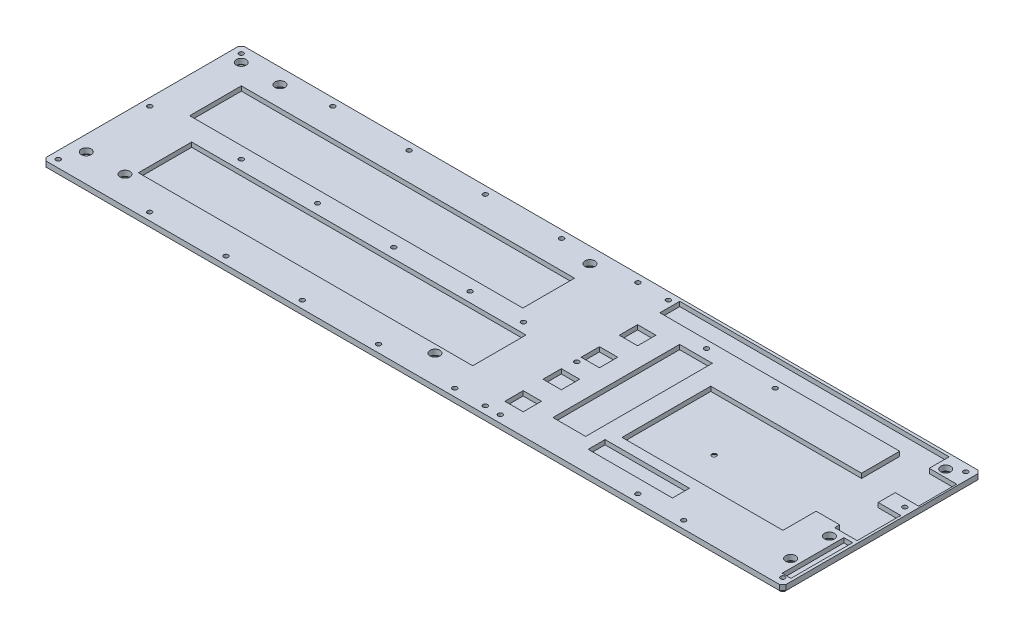
SolidWorks part; units mm, degrees
ref_plane "Front Plane" through (0, 0, 0) normal (0, 0, 1) x (1, 0, 0)
ref_plane "Top Plane" through (0, 0, 0) normal (0, 1, 0) x (1, 0, 0)
ref_plane "Right Plane" through (0, 0, 0) normal (1, 0, 0) x (0, 0, -1)
sketch "Sketch1" plane through (0, 0, 0) normal (0, 1, 0) x (1, 0, 0)
  line L1 (-180, 70) -> (305, 70)
  line L2 (-180, 70) -> (-180, -60)
  line L3 (-180, -60) -> (305, -60)
  line L4 (305, 70) -> (305, -60)
extrude "Boss-Extrude1" add sketch "Sketch1" against normal blind 5 from offset 1.6 offset against normal yes
sketch "Sketch2" plane through (0, -1.6, 0) normal (0, 1, 0) x (1, 0, 0)
  line L2 (-180, 70) -> (-180, -60) construction
  circle A2 centre (-170, 60) radius 3.25
  circle A3 centre (-144.6097, 60) radius 3.25
  circle A4 centre (58.6, 60) radius 3.25
  circle A7 centre (300, -55) radius 1.5
  circle A8 centre (-170, -41.609) radius 3.25
  circle A9 centre (-144.6097, -41.609) radius 3.25
  circle A10 centre (58.6, -41.6) radius 3.25
  circle A11 centre (-175, 65) radius 1.5
  circle A12 centre (-115, 65) radius 1.5
  circle A13 centre (-65, 65) radius 1.5
  circle A14 centre (-15, 65) radius 1.5
  circle A15 centre (35, 65) radius 1.5
  circle A16 centre (85, 65) radius 1.5
  circle A17 centre (105, 65) radius 1.5
  circle A18 centre (300, 65) radius 1.5
  circle A19 centre (85, -55) radius 1.5
  circle A20 centre (105, -55) radius 1.5
  circle A21 centre (205, -55) radius 1.5
  circle A22 centre (235, -55) radius 1.5
  circle A23 centre (-175, -55) radius 1.5
  circle A24 centre (-115, -55) radius 1.5
  circle A25 centre (-65, -55) radius 1.5
  circle A26 centre (-15, -55) radius 1.5
  circle A27 centre (35, -55) radius 1.5
  circle A28 centre (-175, 5) radius 1.5
  circle A31 centre (110, 0) radius 1.5
  circle A34 centre (205, -5) radius 1.5
  circle A35 centre (145, 50) radius 1.5
  circle A36 centre (190, 50) radius 1.5
  circle A37 centre (300, 25) radius 1.5
  circle A49 centre (114.99, -55.1047) radius 1.5
  circle A50 centre (291.7689, -41.609) radius 3.25
  circle A51 centre (291.8, -16.2) radius 3.25
  circle A55 centre (69.99, 4.9953) radius 1.5
  circle A56 centre (35, 4.9953) radius 1.5
  circle A59 centre (-15, 4.9953) radius 1.5
  circle A61 centre (-65, 4.9953) radius 1.5
  circle A62 centre (-115.01, 4.9953) radius 1.5
  circle A64 centre (291.8, 60) radius 3.25
  circle A65 centre (58.6, -41.6) radius 3 construction
  point P4 (0, 0)
  point P5 (0, 0)
  dimension "D1" = 6.5
  dimension "D2" = 3
  dimension "D4" = 20
  dimension "D5" = 265
extrude "Cut-Extrude1" cut sketch "Sketch2" against normal through all
sketch "Sketch3" plane through (0, -1.6, 0) normal (0, 1, 0) x (1, 0, 0)
  line L0 (305, 70) -> (-180, 70) construction
  line L3 (266.5908, 55.0476) -> (303.9819, 55.0476)
  line L4 (266.5908, 55.0476) -> (266.5908, 30.0739)
  line L5 (266.5908, 30.0739) -> (303.9819, 30.0739)
  line L6 (303.9819, 55.0476) -> (303.9819, 30.0739)
  line L7 (288.6671, 18.9249) -> (303.4386, 18.9249)
  line L8 (288.6671, 18.9249) -> (288.6671, -9.6619)
  line L9 (288.6671, -9.6619) -> (303.4386, -9.6619)
  line L10 (303.4386, 18.9249) -> (303.4386, -9.6619)
  line L11 (297.3726, -12.3054) -> (303.1307, -12.3054)
  line L12 (297.3726, -12.3054) -> (297.3726, -52.7789)
  line L13 (297.3726, -52.7789) -> (303.1307, -52.7789)
  line L14 (303.1307, -12.3054) -> (303.1307, -52.7789)
  line L27 (108.8347, 41) -> (120.8347, 41)
  line L28 (108.8347, 41) -> (108.8347, 29)
  line L29 (108.8347, 29) -> (120.8347, 29)
  line L30 (120.8347, 41) -> (120.8347, 29)
  line L35 (133.8233, 43.5526) -> (139.6368, 43.5526)
  line L36 (133.8233, 43.5526) -> (133.8233, -39.498)
  line L37 (133.8233, -39.498) -> (139.6368, -39.498)
  line L39 (149.7413, 43.5526) -> (155.278, 43.5526)
  line L41 (149.7413, -39.498) -> (155.278, -39.498)
  line L42 (155.278, 43.5526) -> (155.278, -39.498)
  line L47 (108.8347, 16) -> (120.8347, 16)
  line L48 (108.8347, 16) -> (108.8347, 4)
  line L49 (108.8347, 4) -> (120.8347, 4)
  line L50 (120.8347, 16) -> (120.8347, 4)
  line L51 (108.8347, -9) -> (120.8347, -9)
  line L52 (108.8347, -9) -> (108.8347, -21)
  line L53 (108.8347, -21) -> (120.8347, -21)
  line L54 (120.8347, -9) -> (120.8347, -21)
  line L55 (108.8347, -34) -> (120.8347, -34)
  line L56 (108.8347, -34) -> (108.8347, -46)
  line L57 (108.8347, -46) -> (120.8347, -46)
  line L58 (120.8347, -34) -> (120.8347, -46)
  line L69 (139.6368, 43.5526) -> (149.7413, 43.5526)
  line L71 (139.6368, -39.498) -> (149.7413, -39.498)
  line L72 (-156.6112, 46.6815) -> (61.7966, 46.6815)
  line L73 (-156.6112, 46.6815) -> (-156.6112, 12.8047)
  line L74 (-156.6112, 12.8047) -> (61.7966, 12.8047)
  line L75 (61.7966, 46.6815) -> (61.7966, 12.8047)
  line L76 (-141.024, -1.495) -> (78.1412, -1.495)
  line L77 (-141.024, -1.495) -> (-141.024, -36.3932)
  line L78 (-141.024, -36.3932) -> (78.1412, -36.3932)
  line L79 (78.1412, -1.495) -> (78.1412, -36.3932)
  line L80 (167.7464, 30.0739) -> (273.2745, 30.0739)
  line L81 (167.7464, 30.0739) -> (167.7464, -28.1467)
  line L82 (167.7464, -28.1467) -> (273.2745, -28.1467)
  line L83 (273.2745, 30.0739) -> (273.2745, -28.1467)
  line L84 (163.4161, -34.9071) -> (218.6974, -34.9071)
  line L85 (163.4161, -34.9071) -> (163.4161, -46)
  line L86 (163.4161, -46) -> (218.6974, -46)
  line L87 (218.6974, -34.9071) -> (218.6974, -46)
  line L88 (273.2745, 30.0739) -> (288.6671, 30.0739)
  line L89 (273.2745, 30.0739) -> (273.2745, -6.4039)
  line L90 (273.2745, -6.4039) -> (288.6671, -6.4039)
  line L91 (288.6671, 30.0739) -> (288.6671, -6.4039)
  line L96 (109.3993, 68.0736) -> (285.9968, 68.0736)
  line L97 (109.3993, 68.0736) -> (109.3993, 55.0476)
  line L98 (109.3993, 55.0476) -> (285.9968, 55.0476)
  line L99 (285.9968, 68.0736) -> (285.9968, 55.0476)
  circle A3 centre (264, 65) radius 1.3177
  circle A4 centre (264, 58) radius 1.3177
  point P46 (288.3592, -6.4039)
  point P47 (167.7464, -28.1467)
  point P48 (61.7966, 12.8047)
  circle M25 centre (105, 65) radius 1.5
  circle M36 centre (205, -5) radius 1.5
  dimension "D3" = 12
  dimension "D4" = 25
  dimension "D5" = 25
  dimension "D6" = 25
  dimension "D7" = 29
extrude "Cut-Extrude2" cut sketch "Sketch3" against normal blind 3 contours L75 L72 L73 L74 | L79 L76 L77 L78 | L99 L96 L97 L98 L3 A4 A3 M25 | L30 L27 L28 L29 | L50 L47 L48 L49 | L54 L51 L52 L53 | L58 L55 L56 L57 | L37 L71 L41 L42 L39 L69 L35 L36 | L87 L84 L85 L86 | L83 L5 L80 L81 L82 M36 | L6 L3 L4 L5 | L91 L5 L83 L90 L8 | L10 L7 L8 L9 | L14 L11 L12 L13 | A4 | A3 region at (197.3821, -1.6, -61.5609) region at (285.2863, -1.6, -42.5608) region at (220.5283, -1.6, -0.9705) region at (280.9708, -1.6, -11.835) region at (296.0529, -1.6, -4.6315) region at (300.2517, -1.6, 32.5421) region at (114.8347, -1.6, -35) region at (144.5507, -1.6, -2.0273) region at (114.8347, -1.6, -10) region at (114.8347, -1.6, 15) region at (114.8347, -1.6, 40) region at (-47.4073, -1.6, -29.7431) region at (-31.4414, -1.6, 18.9441) region at (191.0567, -1.6, 40.4535) region at (264, -1.6, -65) region at (264, -1.6, -58)
chamfer "Chamfer1" distance 2 angle 45 4 edges at (-180, -4.1, -70) (305, -4.1, -70) (305, -4.1, 60) (-180, -4.1, 60)
chamfer "Chamfer3" distance 1.5 angle 45 47 edges at (-179, -6.6, 59) (62.5, -6.6, 60) (304, -6.6, 59) (305, -6.6, -5) (304, -6.6, -69) (62.5, -6.6, -70) (-179, -6.6, -69) (-180, -6.6, -5) (291.8, -6.6, -56.75) (-115.01, -6.6, -3.4953) (300, -6.6, -23.5) (190, -6.6, -48.5) (205, -6.6, 6.5) (145, -6.6, -48.5) (-65, -6.6, -3.4953) (-15, -6.6, -3.4953) (291.8, -6.6, 19.45) (114.99, -6.6, 56.6047) (291.7689, -6.6, 44.859) (-144.6097, -6.6, 44.859) (58.6, -6.6, 44.85) (-175, -6.6, -63.5) (-115, -6.6, -63.5) (-65, -6.6, -63.5) (-15, -6.6, -63.5) (35, -6.6, -63.5) (85, -6.6, -63.5) (58.6, -6.6, -56.75) (-144.6097, -6.6, -56.75) (69.99, -6.6, -3.4953) (-170, -6.6, -56.75) (35, -6.6, -3.4953) (300, -6.6, 56.5) (-170, -6.6, 44.859) (-175, -6.6, -3.5) (35, -6.6, 56.5) (-15, -6.6, 56.5) (-65, -6.6, 56.5) (110, -6.6, 1.5) (105, -6.6, -63.5) (300, -6.6, -63.5) (85, -6.6, 56.5) (105, -6.6, 56.5) (205, -6.6, 56.5) (235, -6.6, 56.5) (-175, -6.6, 56.5) (-115, -6.6, 56.5)
